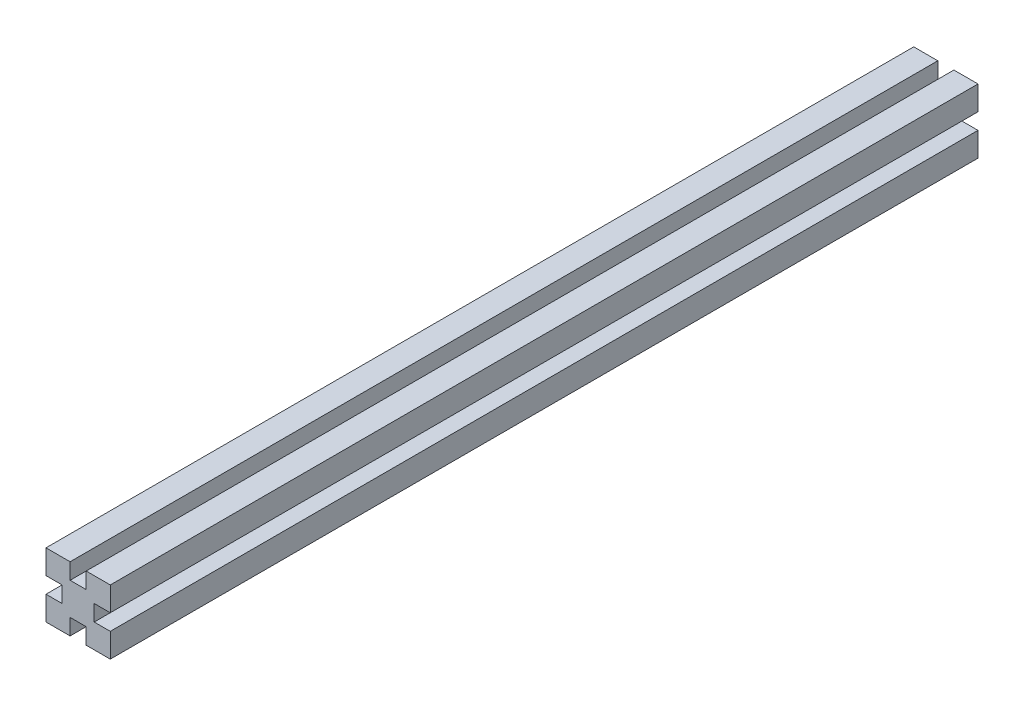
SolidWorks part; units mm, degrees
ref_plane "Front Plane" through (0, 0, 0) normal (0, 0, 1) x (1, 0, 0)
ref_plane "Top Plane" through (0, 0, 0) normal (0, 1, 0) x (1, 0, 0)
ref_plane "Right Plane" through (0, 0, 0) normal (1, 0, 0) x (0, 0, -1)
sketch "Sketch1" plane through (0, 0, 0) normal (0, 0, 1) x (1, 0, 0)
  line L1 (-10, 10) -> (10, 10)
  line L2 (-10, 10) -> (-10, -10)
  line L3 (-10, -10) -> (10, -10)
  line L4 (10, 10) -> (10, -10)
  line L5 (-10, 10) -> (10, -10) construction
  line L6 (-10, -10) -> (10, 10) construction
  line L7 (-2.5, 15) -> (2.5, 15)
  line L8 (-2.5, 15) -> (-2.5, 5)
  line L9 (-2.5, 5) -> (2.5, 5)
  line L10 (2.5, 15) -> (2.5, 5)
  line L11 (-2.5, 15) -> (2.5, 5) construction
  line L12 (-2.5, 5) -> (2.5, 15) construction
  point P0 (0, 0)
  point P6 (0, 10)
  dimension "D1" = 20
  dimension "D2" = 20
  dimension "D3" = 5
  dimension "D4" = 10
extrude "Boss-Extrude1" add sketch "Sketch1" against normal blind 270 contours L1 L10 L9 L8 L2 L3 L4 | L10 L1 L8 L9 region at (0, -0.5, 0) region at (0, 7.5, 0)
extrude "Cut-Extrude1" cut sketch "Sketch1<3>" against normal blind 645 contours L8 L9 L10 L7
sketch "Sketch1<3>" plane through (0, 0, 0) normal (0, 0, 1) x (1, 0, 0) same geometry as "Sketch1"
ref_axis "Axis1" through (0, 0, 32.25) along (0, 0, -1)
pattern_circular "CirPattern1" count 4 over 360 about axis through (0, 0, 32.25) along (0, 0, -1) of "Cut-Extrude1"
